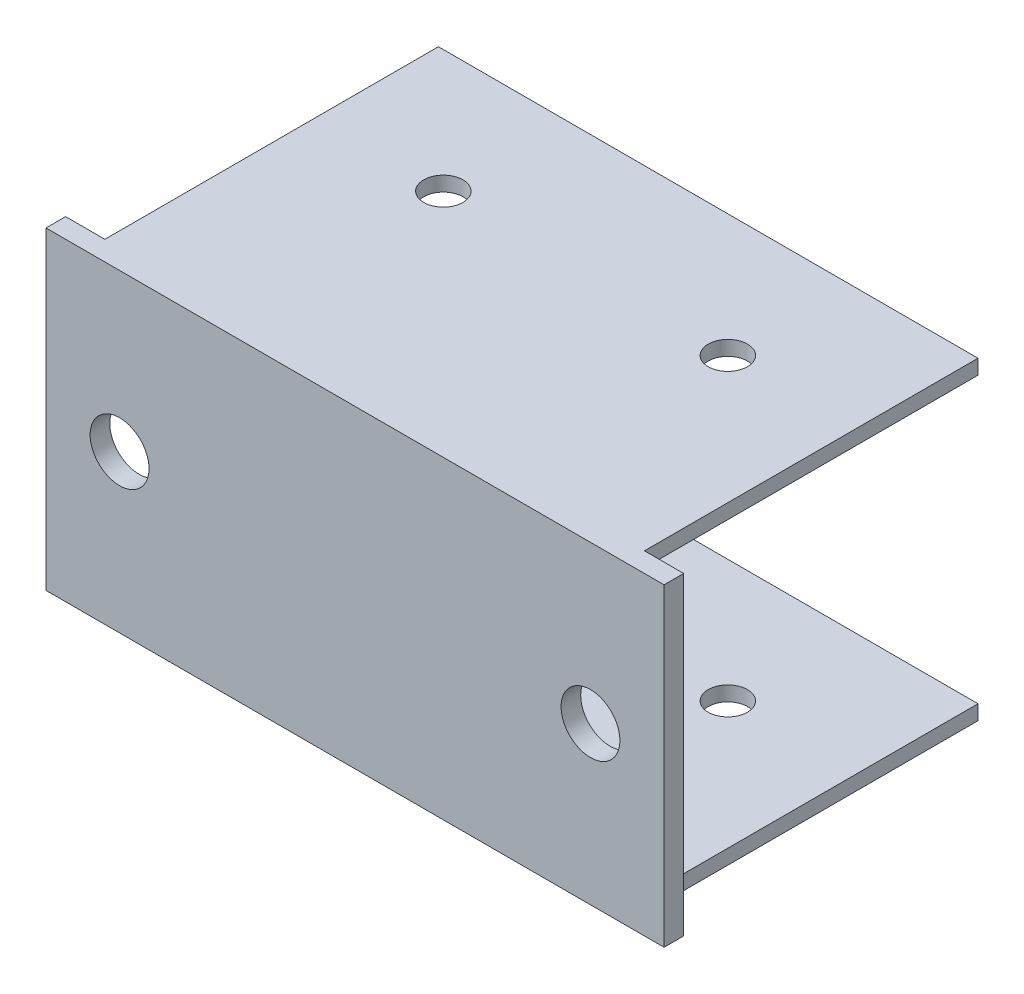
SolidWorks part; units mm, degrees
ref_plane "前视基准面" through (0, 0, 0) normal (0, 0, 1) x (1, 0, 0)
ref_plane "上视基准面" through (0, 0, 0) normal (0, 1, 0) x (1, 0, 0)
ref_plane "右视基准面" through (0, 0, 0) normal (1, 0, 0) x (0, 0, -1)
sketch "草图1" plane through (0, 0, 0) normal (0, 0, 1) x (1, 0, 0)
  line L1 (-31.5, 16) -> (31.5, 16)
  line L2 (-31.5, 16) -> (-31.5, -16)
  line L3 (-31.5, -16) -> (31.5, -16)
  line L4 (31.5, 16) -> (31.5, -16)
  line L5 (-31.5, 16) -> (31.5, -16) construction
  line L6 (-31.5, -16) -> (31.5, 16) construction
  point P0 (0, 0)
  dimension "D1" = 63
  dimension "D2" = 32
extrude "凸台-拉伸1" add sketch "草图1" along normal blind 2 contours L2 L3 L4 L1
sketch "草图2" plane through (0, 0, 2) normal (0, 0, 1) x (1, 0, 0)
  line L0 (-24, 0) -> (24, 0) construction
  circle A0 centre (-24, 0) radius 3
  circle A1 centre (24, 0) radius 3
  point P2 (0, 0)
  dimension "D2" = 6
  dimension "D3" = 6
  dimension "D1" = 48
extrude "切除-拉伸1" cut sketch "草图2" against normal blind 10
sketch "草图4" plane through (0, 16, 0) normal (0, 1, 0) x (1, 0, 0)
  line L0 (-31.5, -2) -> (31.5, -2) construction
  line L1 (-27.5, 34) -> (27.5, 34)
  line L2 (-27.5, 34) -> (-27.5, -2)
  line L3 (-27.5, -2) -> (27.5, -2)
  line L4 (27.5, 34) -> (27.5, -2)
  line L5 (-27.5, 34) -> (27.5, -2) construction
  line L6 (-27.5, -2) -> (27.5, 34) construction
  point P0 (0, 16)
  dimension "D1" = 36
  dimension "D2" = 55
extrude "凸台-拉伸2" add sketch "草图4" against normal blind 1.5
sketch "草图5" plane through (0, 16, 0) normal (0, 1, 0) x (1, 0, 0)
  line L0 (-14.5, 21.5) -> (14.5, 21.5) construction
  line L1 (27.5, 34) -> (-27.5, 34) construction
  circle A0 centre (-14.5, 21.5) radius 2
  circle A1 centre (14.5, 21.5) radius 2
  point P2 (0, 21.5)
  dimension "D3" = 4
  dimension "D4" = 4
  dimension "D1" = 12.5
  dimension "D2" = 29
extrude "切除-拉伸2" cut sketch "草图5" against normal through all
mirror "镜向1" about plane through (0, 0, 0) normal (0, 1, 0) of "切除-拉伸2", "凸台-拉伸2"
